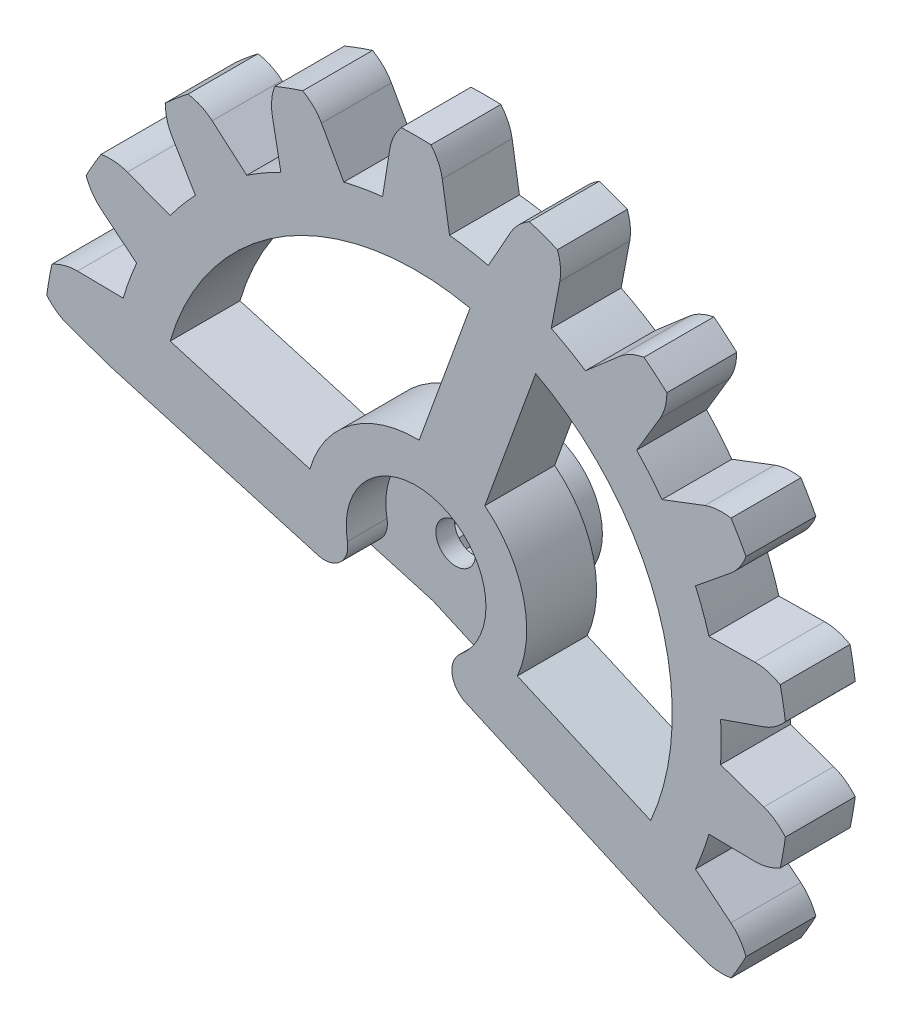
SolidWorks part; units mm, degrees
note: The reader was unsure of these and kept them because the rebuilt part matched: shared geometry of "Sketch2<4>".
ref_plane "Front Plane" through (0, 0, 0) normal (0, 0, 1) x (1, 0, 0)
ref_plane "Top Plane" through (0, 0, 0) normal (0, 1, 0) x (1, 0, 0)
ref_plane "Right Plane" through (0, 0, 0) normal (1, 0, 0) x (0, 0, -1)
sketch "Sketch2" plane through (0, 0, 0) normal (0, 0, 1) x (1, 0, 0)
  line L0 (0, 0) -> (0, 4.5292) construction
  line L1 (0, 2) -> (0.3742, 1.7607)
  line L2 (2.6643, 5.984) -> (0, 0) construction
  line L3 (0.3742, 1.7607) -> (0.8135, 1.8271)
  line L4 (0.3742, 1.7607) -> (0.4158, 1.9563)
  line L33 (0.8135, 1.8271) -> (1.058, 1.4562)
  line L34 (1.058, 1.4562) -> (1.4863, 1.3383)
  line L35 (1.4863, 1.3383) -> (1.5588, 0.9)
  line L36 (1.5588, 0.9) -> (1.9021, 0.618)
  line L37 (1.9021, 0.618) -> (1.7901, 0.1882)
  line L38 (1.7901, 0.1882) -> (1.989, -0.2091)
  line L39 (1.989, -0.2091) -> (1.7119, -0.5562)
  line L40 (1.7119, -0.5562) -> (1.7321, -1)
  line L41 (1.7321, -1) -> (1.3377, -1.2044)
  line L42 (1.3377, -1.2044) -> (1.1756, -1.618)
  line L43 (1.1756, -1.618) -> (0.7321, -1.6444)
  line L44 (0.7321, -1.6444) -> (0.4158, -1.9563)
  line L45 (0.4158, -1.9563) -> (0, -1.8)
  line L46 (0, -1.8) -> (-0.4158, -1.9563)
  line L47 (-0.4158, -1.9563) -> (-0.7321, -1.6444)
  line L48 (-0.7321, -1.6444) -> (-1.1756, -1.618)
  line L49 (-1.1756, -1.618) -> (-1.3377, -1.2044)
  line L50 (-1.3377, -1.2044) -> (-1.7321, -1)
  line L51 (-1.7321, -1) -> (-1.7119, -0.5562)
  line L52 (-1.7119, -0.5562) -> (-1.989, -0.2091)
  line L53 (-1.989, -0.2091) -> (-1.7901, 0.1882)
  line L54 (-1.7901, 0.1882) -> (-1.9021, 0.618)
  line L55 (-1.9021, 0.618) -> (-1.5588, 0.9)
  line L56 (-1.5588, 0.9) -> (-1.4863, 1.3383)
  line L57 (-1.4863, 1.3383) -> (-1.058, 1.4562)
  line L58 (-1.058, 1.4562) -> (-0.8135, 1.8271)
  line L59 (-0.8135, 1.8271) -> (-0.3742, 1.7607)
  line L60 (-0.3742, 1.7607) -> (0, 2)
  line L61 (0.15, 2.9962) -> (20.1, 1.9975)
  line L62 (0.15, -2.9962) -> (20.1, -1.9975)
  circle A0 centre (0, 0) radius 2.8
  circle A1 centre (0, 0) radius 3
  circle A2 centre (0, 0) radius 2 construction
  circle A3 centre (0, 0) radius 0.85
  circle A4 centre (0, 0) radius 2.15
  circle A5 centre (20, 0) radius 2
  circle A6 centre (20, 0) radius 0.5
  circle A7 centre (17, 0) radius 0.5
  circle A8 centre (14, 0) radius 0.5
  circle A9 centre (11, 0) radius 0.5
  point P11 (0.8135, 1.8271)
  point P57 (0, 0)
  dimension "D1" = 6
  dimension "D2" = 5.6
  dimension "D3" = 4
  dimension "D7" = 1.7
  dimension "D9" = 4.3
  dimension "D10" = 4
  dimension "D12" = 1
  dimension "D4" = 24
  dimension "D5" = 12
  dimension "D6" = 0.2
  dimension "D11" = 20
  dimension "D13" = 3
  dimension "D14" = 3
  dimension "D15" = 3
  dimension "D8" = 15
extrude "Boss-Extrude3" add sketch "Sketch2<4>" along normal blind 2.5 from offset 2.7
sketch "Sketch2<4>" plane through (0, 0, 0) normal (0, 0, 1) x (1, 0, 0) same geometry as "Sketch2"
extrude "Boss-Extrude4" add sketch "Sketch2" along normal up to surface (5.2 mm away) up to face at (2.15, 0, 5.2)
sketch "Sketch3" plane through (0, 0, 5.2) normal (0, 0, 1) x (1, 0, 0)
  line L0 (0, 0) -> (17.0784, 3.0114) construction
  line L1 (0, 0) -> (15.8557, 2.1438) construction
  line L2 (0, 0) -> (15.9209, 1.5891) construction
  line L3 (0, 0) -> (15.9666, 1.0325) construction
  line L4 (13.0727, 0.8454) -> (14.9258, 1.4898)
  line L5 (0, 0) -> (16, 0) construction
  line L6 (13.1, 0) -> (0, 0)
  line L7 (12.5734, 3.6767) -> (14.5352, 3.705)
  line L8 (12.31, 4.4805) -> (0, 0)
  circle A0 centre (0, 0) radius 14.6 construction
  circle A1 centre (0, 0) radius 16 construction
  circle A2 centre (0, 0) radius 13.1 construction
  arc A3 (13.0727, 0.8454) -> (13.1, 0) centre (0, 0) cw
  arc A4 (15.8557, 2.1438) -> (15.6327, 3.4085) centre (0, 0) ccw
  arc A5 (12.5734, 3.6767) -> (12.31, 4.4805) centre (0, 0) ccw
  spline S0 degree 2 poles (14.9258, 1.4898) (15.4415, 1.6691) (15.8557, 2.1438) knots 0 0 0 1 1 1
  spline S1 degree 2 poles (14.5352, 3.705) (15.0811, 3.7128) (15.6327, 3.4085) knots 0 0 0 1 1 1
  dimension "D1" = 29.2
  dimension "D2" = 32
  dimension "D3" = 26.2
  dimension "D4" = 15
  dimension "D5" = 3.7
  dimension "D6" = 2
  dimension "D7" = 2
  dimension "D8" = 2.3
extrude "Boss-Extrude5" add sketch "Sketch3" against normal blind 3 separate body
pattern_circular "CirPattern1" count 18 over 360 about axis through (0, 0, 5.2) along (0, 0, 1) of bodies 106
combine bodies "Combine1" bodies to combine 112 111 110 109 108 107 106 123 122 121 120 119 118 117 116 115 114 113
sketch "Sketch4" plane through (0, 0, 5.2) normal (0, 0, 1) x (1, 0, 0)
  line L0 (-13.0727, 0.8454) -> (-0.9577, -2.6311)
  line L1 (10.5577, -7.7554) -> (-0.9577, -2.6311)
  line L4 (-13.0727, 0.8454) -> (-15.8954, 1.8269)
  line L5 (10.5577, -7.7554) -> (13.3509, -8.8178)
  line L6 (10.5577, -7.7554) -> (12.3915, -8.4529) construction
  line L7 (-13.0727, 0.8454) -> (-14.9258, 1.4898) construction
  arc A1 (-4.8645, 15.2426) -> (-6.0713, 14.8034) centre (0, 0) ccw construction
  circle A2 centre (0, 0) radius 16 construction
  arc A3 (-15.8954, 1.8269) -> (13.3509, -8.8178) centre (0, 0) ccw
  circle A4 centre (0, 0) radius 2.8 construction
combine bodies "Combine2" operation type add bodies to combine 124 104
extrude "Cut-Extrude3" cut sketch "Sketch4" against normal blind 3 contours L0 L1 L5 A3 L4
sketch "Sketch5" plane through (0, 0, 5.2) normal (0, 0, 1) x (1, 0, 0)
  circle A0 centre (0, 0) radius 3
  dimension "D1" = 6
extrude "Cut-Extrude4" cut sketch "Sketch5" against normal blind 1.7
sketch "Sketch6" plane through (0, 0, 5.2) normal (0, 0, 1) x (1, 0, 0)
  line L0 (0, 0) -> (-12.5734, 3.6767) construction
  line L1 (0, 0) -> (5.4723, 15.0351) construction
  line L2 (2.3175, 10.7531) -> (0.1319, 4.7482)
  line L3 (-10.5579, 3.0873) -> (-4.5591, 1.3332)
  line L4 (10.0723, -4.4214) -> (4.3494, -1.9093)
  line L5 (5.1366, 9.727) -> (2.951, 3.7221)
  arc A0 (6.0713, 14.8034) -> (4.8645, 15.2426) centre (0, 0) ccw construction
  circle A1 centre (0, 0) radius 4.75 construction
  circle A2 centre (0, 0) radius 11 construction
  arc A3 (0.1319, 4.7482) -> (-4.5591, 1.3332) centre (0, 0) ccw
  arc A4 (2.3175, 10.7531) -> (-10.5579, 3.0873) centre (0, 0) ccw
  arc A5 (2.951, 3.7221) -> (4.3494, -1.9093) centre (0, 0) cw
  arc A6 (5.1366, 9.727) -> (10.0723, -4.4214) centre (0, 0) cw
  dimension "D1" = 9.5
  dimension "D2" = 22
  dimension "D3" = 1.5
extrude "Cut-Extrude5" cut sketch "Sketch6" against normal blind 10 contours L2 A4 L3 A3 | A6 L5 A5 L4
fillet "Fillet1" radius 1 2 edges at (-0.1356, -2.9969, 4.35) (-1.8225, -2.383, 4.35)
